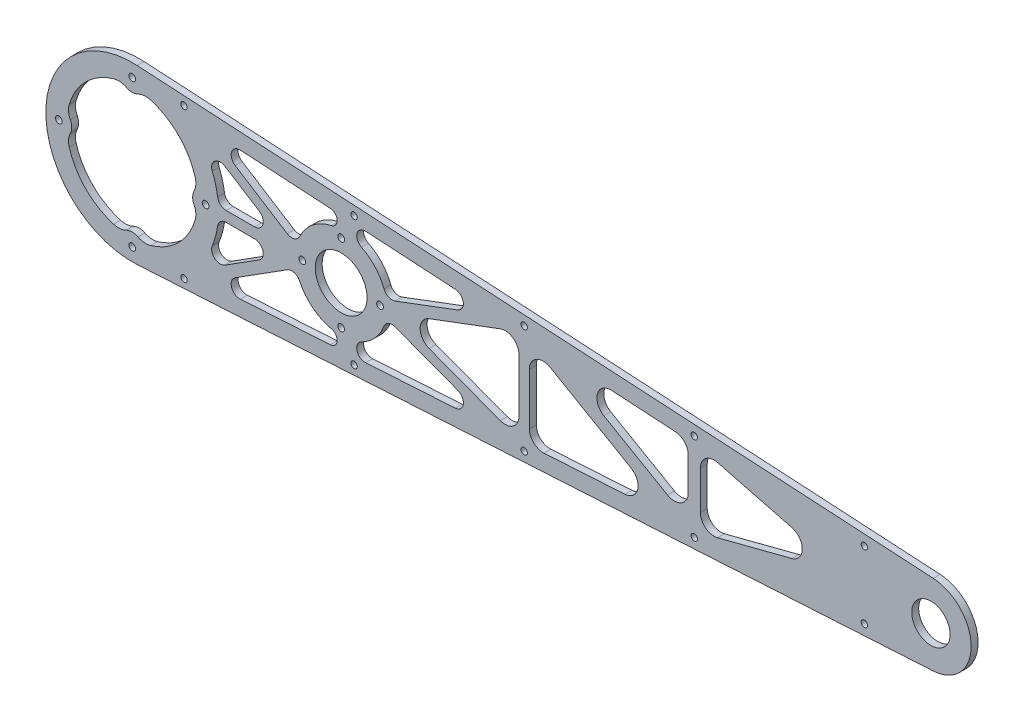
SolidWorks part; units mm, degrees
ref_plane "Front Plane" through (0, 0, 0) normal (0, 0, 1) x (1, 0, 0)
ref_plane "Top Plane" through (0, 0, 0) normal (0, 1, 0) x (1, 0, 0)
ref_plane "Right Plane" through (0, 0, 0) normal (1, 0, 0) x (0, 0, -1)
sketch "Sketch1" plane through (0, 0, 0) normal (0, 0, 1) x (1, 0, 0)
  line L0 (-231.25, 0) -> (231.25, 0) construction
  line L1 (-228.3622, 49.9165) -> (232.595, 23.2486)
  line L2 (-228.3622, -49.9165) -> (232.595, -23.2486)
  line L3 (191.25, 20.6322) -> (-201.25, 43.3396) construction
  circle A0 centre (231.25, 0) radius 11.1125
  arc A1 (232.595, 23.2486) -> (232.595, -23.2486) centre (231.25, 0) cw
  circle A2 centre (-231.25, 0) radius 42.5 construction
  circle A3 centre (-110.25, 0) radius 22.5 construction
  arc A4 (-228.3622, 49.9165) -> (-228.3622, -49.9165) centre (-231.25, 0) ccw
  circle A5 centre (-231.25, 42.5) radius 1.75 construction
  circle A6 centre (-231.25, 0) radius 30
  circle A7 centre (-110.25, 0) radius 15
  circle A8 centre (231.25, 0) radius 35.306 construction
  circle A9 centre (-201.25, 43.3396) radius 1.85
  circle A10 centre (-102.7635, 37.3743) radius 1.85
  circle A11 centre (-4.277, 31.4089) radius 1.85
  circle A12 centre (94.2095, 25.4436) radius 1.85
  circle A13 centre (192.696, 19.4782) radius 1.85
  circle A14 centre (291.1825, 13.5129) radius 1.85 construction
  circle A15 centre (192.696, -19.4782) radius 1.85
  circle A16 centre (94.2095, -25.4436) radius 1.85
  circle A17 centre (-4.277, -31.4089) radius 1.85
  circle A18 centre (-102.7635, -37.3743) radius 1.85
  circle A19 centre (-201.25, -43.3396) radius 1.85
  point P4 (0, 0)
  point P15 (-231.25, 44.25)
  point P16 (-273.75, 0)
  point P17 (-231.25, 50)
  point P18 (-110.25, 22.5)
  point P19 (-231.25, -42.5)
  point P20 (-188.75, 0)
  point P21 (-132.75, 0)
  point P22 (-110.25, -22.5)
  point P23 (-87.75, 0)
  dimension "D2" = 22.225
  dimension "D3" = 85
  dimension "D5" = 45
  dimension "D6" = 3.5
  dimension "D7" = 7.5
  dimension "D8" = 23.2875
  dimension "D9" = 60
  dimension "D10" = 30
  dimension "D11" = 70.612
  dimension "D13" = 3.7
  dimension "D16" = 6
  dimension "D1" = 462.5
  dimension "D4" = 121
  dimension "D12" = 5
  dimension "D14" = 30
  dimension "D15" = 40
extrude "Boss-Extrude1" add sketch "Sketch1" along normal blind 4
sketch "Sketch4" plane through (0, 0, 4) normal (0, 0, 1) x (1, 0, 0)
  point P0 (-231.25, 42.5)
  point P7 (-188.75, 0)
  point P10 (-132.75, 0)
  point P13 (-110.25, 22.5)
  point P16 (-87.75, 0)
  point P19 (-110.25, -22.5)
  point P24 (-273.75, 0)
  point P28 (-231.25, -42.5)
hole_wizard "M3.5 Clearance Hole1" positions "Sketch4" profile "Sketch6" hole size "M3.5" standard "ANSI Metric" end condition up to next
sketch "Sketch6" plane through (-231.25, 42.5, 4) normal (1, 0, 0) x (0, -1, 0)
  line L0 (0, 0) -> (0, 4)
  line L1 (0, 4) -> (1.95, 4)
  line L2 (1.95, 4) -> (1.95, 0)
  line L5 (1.95, 0) -> (0, 0)
  line L11 (0, -6.35) -> (0, 107.95) construction
  dimension "Thru Hole Dia." = 3.9
  dimension "Thru Hole Depth" = 4
sketch "Sketch7" plane through (0, 0, 4) normal (0, 0, 1) x (1, 0, 0)
  line L0 (94.2095, 25.4436) -> (94.2095, -25.4436) construction
  line L1 (94.2095, -25.4436) -> (192.696, 0) construction
  line L2 (192.696, 0) -> (94.2095, 25.4436) construction
  line L3 (192.696, 0) -> (-87.75, 0) construction
  line L4 (192.696, -19.4782) -> (192.696, 19.4782) construction
  line L5 (107.7105, 18.8571) -> (150.7205, 7.7457)
  line L6 (150.7205, -7.7457) -> (107.7105, -18.8571)
  line L7 (97.7095, -11.1115) -> (97.7095, 11.1115)
  line L8 (-4.277, -31.4089) -> (-4.277, 31.4089) construction
  line L9 (-4.277, 31.4089) -> (94.2095, -25.4436) construction
  line L10 (-4.277, 31.4089) -> (94.2095, 25.4436) construction
  line L11 (-4.277, -31.4089) -> (94.2095, -25.4436) construction
  line L12 (-87.75, 0) -> (-102.7635, 37.3743) construction
  line L13 (-102.7635, 37.3743) -> (-4.277, 31.4089) construction
  line L14 (-4.277, 31.4089) -> (-87.75, 0) construction
  line L15 (90.7095, -4.9492) -> (90.7095, 14.1182)
  line L16 (83.1932, 22.1035) -> (46.2904, 24.3387)
  line L17 (41.8072, 9.4249) -> (78.7099, -11.8777)
  line L18 (10.7225, 18.1316) -> (57.6374, -8.9506)
  line L19 (54.1216, -23.8644) -> (7.2067, -26.706)
  line L20 (-1.277, -18.7207) -> (-1.277, 11.2032)
  line L22 (-228.3622, -49.9165) -> (232.595, -23.2486) construction
  line L23 (-7.277, -15.517) -> (-7.277, 15.517)
  line L24 (-18.0944, 23.0044) -> (-59.3325, 7.4875)
  line L25 (-59.3325, -7.4875) -> (-18.0944, -23.0044)
  line L27 (-79.0341, 6.4849) -> (-42.7227, 20.1481)
  line L28 (-44.1812, 29.8186) -> (-96.0994, 32.9633)
  line L32 (-132.75, 0) -> (-188.75, 0) construction
  line L33 (-188.75, 0) -> (-201.25, 43.3396) construction
  line L34 (-201.25, 43.3396) -> (-132.75, 0) construction
  line L35 (-132.75, 0) -> (-102.7635, 37.3743) construction
  line L36 (-102.7635, 37.3743) -> (-201.25, 43.3396) construction
  line L37 (-171.617, 28.141) -> (-141.4788, 9.0727)
  line L39 (-116.5248, 34.2005) -> (-168.6414, 37.3572)
  line L41 (-176.8349, 3) -> (-160.3569, 3)
  line L42 (-157.6835, 12.2253) -> (-177.574, 24.8099)
  line L44 (-116.5248, -34.2005) -> (-168.6414, -37.3572)
  line L45 (-171.617, -28.141) -> (-141.4788, -9.0727)
  line L46 (-157.6835, -12.2253) -> (-177.574, -24.8099)
  line L48 (-176.8349, -3) -> (-160.3569, -3)
  line L50 (-44.1812, -29.8186) -> (-96.0994, -32.9633)
  line L51 (-79.0341, -6.4849) -> (-42.7227, -20.1481)
  line L52 (-102.7635, -37.3743) -> (-110.25, -22.5) construction
  line L53 (-113.0228, -28.1124) -> (-105.6224, -42.8156) construction
  line L54 (-100.7253, -30.3024) -> (-94.7439, -42.1863) construction
  arc A0 (150.7205, 7.7457) -> (150.7205, -7.7457) centre (148.7195, 0) cw
  arc A1 (107.7105, -18.8571) -> (97.7095, -11.1115) centre (105.7095, -11.1115) cw
  arc A2 (107.7105, 18.8571) -> (97.7095, 11.1115) centre (105.7095, 11.1115) ccw
  arc A3 (90.7095, 14.1182) -> (83.1932, 22.1035) centre (82.7095, 14.1182) ccw
  arc A4 (46.2904, 24.3387) -> (41.8072, 9.4249) centre (45.8067, 16.3534) ccw
  arc A5 (90.7095, -4.9492) -> (78.7099, -11.8777) centre (82.7095, -4.9492) cw
  arc A6 (57.6374, -8.9506) -> (54.1216, -23.8644) centre (53.6379, -15.879) cw
  arc A7 (7.2067, -26.706) -> (-1.277, -18.7207) centre (6.723, -18.7207) cw
  arc A8 (10.7225, 18.1316) -> (-1.277, 11.2032) centre (6.723, 11.2032) ccw
  arc A9 (-7.277, -15.517) -> (-18.0944, -23.0044) centre (-15.277, -15.517) cw
  arc A10 (-7.277, 15.517) -> (-18.0944, 23.0044) centre (-15.277, 15.517) ccw
  arc A11 (-59.3325, 7.4875) -> (-59.3325, -7.4875) centre (-56.5152, 0) ccw
  arc A12 (-42.7227, 20.1481) -> (-44.1812, 29.8186) centre (-44.4835, 24.8278) ccw
  arc A18 (-171.617, 28.141) -> (-168.6414, 37.3572) centre (-168.9437, 32.3663) cw
  arc A21 (-160.3569, 3) -> (-157.6835, 12.2253) centre (-160.3569, 8) ccw
  arc A22 (-181.7818, 7.2727) -> (-176.8349, 3) centre (-176.8349, 8) ccw
  arc A23 (-184.8839, 18.7133) -> (-177.574, 24.8099) centre (-180.2473, 20.5846) cw
  arc A26 (-171.617, -28.141) -> (-168.6414, -37.3572) centre (-168.9437, -32.3663) ccw
  arc A27 (-184.8839, -18.7133) -> (-177.574, -24.8099) centre (-180.2473, -20.5846) ccw
  arc A28 (-181.7818, -7.2727) -> (-176.8349, -3) centre (-176.8349, -8) cw
  arc A29 (-160.3569, -3) -> (-157.6835, -12.2253) centre (-160.3569, -8) cw
  circle A30 centre (-110.25, 0) radius 15 construction
  circle A31 centre (-110.25, 0) radius 15 construction
  circle A32 centre (-110.25, 0) radius 22.5 construction
  arc A34 (-85.4703, 9.3925) -> (-98.5366, 23.7707) centre (-110.25, 0) ccw
  arc A37 (-85.4703, 9.3925) -> (-79.0341, 6.4849) centre (-80.7949, 11.1646) ccw
  arc A38 (-42.7227, -20.1481) -> (-44.1812, -29.8186) centre (-44.4835, -24.8278) cw
  arc A39 (-96.0994, -32.9633) -> (-98.5366, -23.7707) centre (-96.3927, -28.1217) cw
  arc A40 (-134.2728, 11.1872) -> (-115.8848, 25.894) centre (-110.25, 0) cw
  arc A41 (-85.4703, -9.3925) -> (-98.5366, -23.7707) centre (-110.25, 0) cw
  arc A42 (-85.4703, -9.3925) -> (-79.0341, -6.4849) centre (-80.7949, -11.1646) cw
  arc A43 (-116.5248, 34.2005) -> (-115.8848, 25.894) centre (-116.779, 30.003) cw
  arc A44 (-134.2728, 11.1872) -> (-141.4788, 9.0727) centre (-138.8054, 13.298) cw
  arc A45 (-116.5248, -34.2005) -> (-115.8848, -25.894) centre (-116.779, -30.003) ccw
  arc A46 (-134.2728, -11.1872) -> (-115.8848, -25.894) centre (-110.25, 0) ccw
  arc A47 (-134.2728, -11.1872) -> (-141.4788, -9.0727) centre (-138.8054, -13.298) ccw
  arc A48 (-96.0994, 32.9633) -> (-98.5366, 23.7707) centre (-96.3927, 28.1217) ccw
  circle A49 centre (-4.277, -31.4089) radius 1.85 construction
  circle A50 centre (-4.277, -31.4089) radius 1.85
  arc A51 (-184.8839, 18.7133) -> (-181.7818, 7.2727) centre (-231.25, 0) cw
  arc A52 (-228.3622, 49.9165) -> (-228.3622, -49.9165) centre (-231.25, 0) ccw construction
  arc A53 (-228.3622, 49.9165) -> (-228.3622, -49.9165) centre (-231.25, 0) ccw
  arc A55 (-184.8839, -18.7133) -> (-181.7818, -7.2727) centre (-231.25, 0) ccw
  point P36 (180.7024, 0)
  point P59 (-79.2314, 0)
  point P102 (-113.0228, -28.1124)
  dimension "D8" = 8
  dimension "D11" = 5
  dimension "D12" = 5
  dimension "D18" = 5
  dimension "D19" = 5
  dimension "D10" = 4
  dimension "D21" = 5
  dimension "D1" = 3
  dimension "D2" = 7
  dimension "D3" = 8
  dimension "D4" = 8
  dimension "D5" = 8
  dimension "D6" = 6
  dimension "D7" = 6
  dimension "D9" = 8
  dimension "D13" = 8
  dimension "D14" = 5
  dimension "D15" = 6
  dimension "D17" = 6
extrude "Cut-Extrude1" cut sketch "Sketch7" against normal blind 10 contours A55 A27 L46 A29 L48 A28 | A23 A51 A22 L41 A21 L42 | A44 A40 A43 L39 A18 L37 | A46 A47 L45 A26 L44 A45 | A42 A41 A39 L50 A38 L51 | L28 A48 A34 A37 L27 A12 | L24 A11 L25 A9 L23 A10 | L18 A8 L20 A7 L19 A6 | L5 A2 L7 A1 L6 A0 | A5 L15 A3 L16 A4 L17 region at (122.1459, 0, 4) region at (68.375, 8.863, 4) region at (24.042, -7.8996, 4) region at (-30.0623, 0, 4) region at (-71.6765, 22.0808, 4) region at (-143.7382, 26.1619, 4) region at (-171.7996, 12.3824, 4) region at (-143.7382, -26.1619, 4) region at (-171.7996, -12.3824, 4) region at (-71.6765, -22.0808, 4)
sketch "Sketch8" plane through (0, 0, 4) normal (0, 0, 1) x (1, 0, 0)
  arc A0 (-267.0517, -3.3738) -> (-267.0517, 3.3738) centre (-273.75, 0) ccw
  arc A1 (-267.7172, 10.6837) -> (-241.9337, 36.4672) centre (-231.25, 0) cw
  arc A2 (-228.3622, 49.9165) -> (-228.3622, -49.9165) centre (-231.25, 0) ccw construction
  arc A3 (-228.3622, 49.9165) -> (-228.3622, -49.9165) centre (-231.25, 0) ccw
  circle A4 centre (-273.75, 0) radius 1.95 construction
  circle A5 centre (-273.75, 0) radius 1.95
  arc A6 (-234.6238, 35.8017) -> (-227.8762, 35.8017) centre (-231.25, 42.5) ccw
  arc A7 (-220.5663, 36.4672) -> (-194.7828, 10.6837) centre (-231.25, 0) cw
  arc A8 (-195.4483, 3.3738) -> (-195.4483, -3.3738) centre (-188.75, 0) ccw
  arc A9 (-194.7828, -10.6837) -> (-220.5663, -36.4672) centre (-231.25, 0) cw
  arc A10 (-227.8762, -35.8017) -> (-234.6238, -35.8017) centre (-231.25, -42.5) ccw
  arc A11 (-241.9337, -36.4672) -> (-267.7172, -10.6837) centre (-231.25, 0) cw
  arc A12 (-241.9337, 36.4672) -> (-234.6238, 35.8017) centre (-239.1222, 26.8706) cw
  arc A13 (-227.8762, 35.8017) -> (-220.5663, 36.4672) centre (-223.3778, 26.8706) cw
  arc A14 (-194.7828, 10.6837) -> (-195.4483, 3.3738) centre (-204.3794, 7.8722) cw
  arc A15 (-195.4483, -3.3738) -> (-194.7828, -10.6837) centre (-204.3794, -7.8722) cw
  arc A16 (-220.5663, -36.4672) -> (-227.8762, -35.8017) centre (-223.3778, -26.8706) cw
  arc A17 (-234.6238, -35.8017) -> (-241.9337, -36.4672) centre (-239.1222, -26.8706) cw
  arc A18 (-267.0517, -3.3738) -> (-267.7172, -10.6837) centre (-258.1206, -7.8722) ccw
  arc A19 (-267.0517, 3.3738) -> (-267.7172, 10.6837) centre (-258.1206, 7.8722) cw
  point P24 (-231.25, 0)
  dimension "D1" = 12
  dimension "D3" = 10
  dimension "D2" = 4
extrude "Cut-Extrude2" cut sketch "Sketch8" against normal blind 10 contours A11 A10 A9 A8 A7 A6 A1 A0 region at (-231.25, 0, 4)
